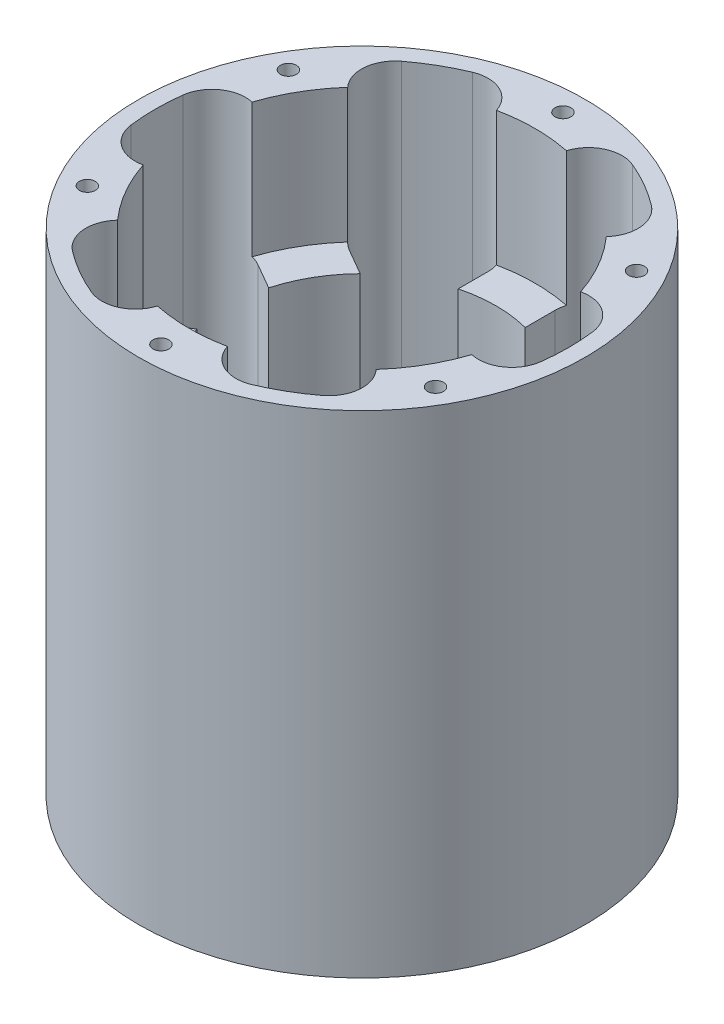
SolidWorks part; units mm, degrees
material "6061-T6 (SS)"
ref_plane "Front Plane" through (0, 0, 0) normal (0, 0, 1) x (1, 0, 0)
ref_plane "Top Plane" through (0, 0, 0) normal (0, 1, 0) x (1, 0, 0)
ref_plane "Right Plane" through (0, 0, 0) normal (1, 0, 0) x (0, 0, -1)
sketch "Sketch1" plane through (0, 0, 0) normal (0, 1, 0) x (1, 0, 0)
  circle A0 centre (0, 0) radius 31.75
  circle A1 centre (0, 0) radius 19.05
  dimension "D1" = 63.5
  dimension "D2" = 38.1
extrude "Boss-Extrude1" add sketch "Sketch1" along normal mid plane 69.85
sketch "Sketch2" plane through (0, 34.925, 0) normal (0, 1, 0) x (1, 0, 0)
  circle A0 centre (0, 0) radius 24.6062
  dimension "D1" = 49.2125
extrude "Cut-Extrude1" cut sketch "Sketch2" against normal blind 19.05
sketch "Sketch3" plane through (0, -34.925, 0) normal (0, -1, 0) x (1, 0, 0)
  circle A0 centre (0, 0) radius 24.6062
  dimension "D1" = 49.2125
extrude "Cut-Extrude2" cut sketch "Sketch3" against normal blind 30.48
hole_wizard "#4-40 Tapped Hole1" positions "Sketch5" profile "Sketch6" tap size "#4-40" standard "Ansi Inch" end condition through all
sketch "Sketch5" plane through (0, 34.925, 0) normal (0, 1, 0) x (-1, 0, 0)
  point P0 (0, 28.575)
  point P13 (24.7467, 14.2875)
  point P14 (24.7467, -14.2875)
  point P15 (0, -28.575)
  point P16 (-24.7467, -14.2875)
  point P17 (-24.7467, 14.2875)
  dimension "D1" = 28.575
  dimension "D2" = 6
sketch "Sketch6" plane through (0, 34.925, 28.575) normal (1, 0, 0) x (0, 0, 1)
  line L0 (0, 0) -> (0, 69.85)
  line L1 (0, 69.85) -> (1.1303, 69.85)
  line L2 (1.1303, 69.85) -> (1.1303, 0)
  line L5 (1.1303, 0) -> (0, 0)
  line L11 (0, -6.35) -> (0, 107.95) construction
  dimension "Thread Major Dia." = 2.2606
  dimension "Thru Tap Drill Depth" = 69.85
sketch "Sketch7" plane through (0, -34.925, 0) normal (0, -1, 0) x (1, 0, 0)
  line L0 (0, 19.05) -> (0, 29.3687) construction
  line L1 (4.7625, 18.4451) -> (4.7625, 28.98)
  line L2 (-4.7625, 18.4451) -> (-4.7625, 28.98)
  line L3 (-4.7625, 19.05) -> (-4.7625, 29.3687) construction
  line L4 (4.7625, 19.05) -> (4.7625, 29.3687) construction
  line L5 (18.3552, 5.0981) -> (27.4787, 10.3656)
  line L6 (16.4978, 9.525) -> (25.4341, 14.6844) construction
  line L7 (13.5927, 13.347) -> (22.7162, 18.6145)
  line L8 (13.5927, -13.347) -> (22.7162, -18.6145)
  line L9 (16.4978, -9.525) -> (25.4341, -14.6844) construction
  line L10 (18.3552, -5.0981) -> (27.4787, -10.3656)
  line L11 (-4.7625, -18.4451) -> (-4.7625, -28.98)
  line L12 (0, -19.05) -> (0, -29.3687) construction
  line L13 (4.7625, -18.4451) -> (4.7625, -28.98)
  line L14 (-18.3552, -5.0981) -> (-27.4787, -10.3656)
  line L15 (-16.4978, -9.525) -> (-25.4341, -14.6844) construction
  line L16 (-13.5927, -13.347) -> (-22.7162, -18.6145)
  line L17 (-13.5927, 13.347) -> (-22.7162, 18.6145)
  line L18 (-16.4978, 9.525) -> (-25.4341, 14.6844) construction
  line L19 (-18.3552, 5.0981) -> (-27.4787, 10.3656)
  arc A0 (-4.7625, 28.98) -> (-22.7162, 18.6145) centre (0, 0) ccw
  circle A1 centre (0, 0) radius 31.75 construction
  arc A2 (13.5927, 13.347) -> (4.7625, 18.4451) centre (0, 0) ccw
  circle A3 centre (0, 0) radius 19.05 construction
  arc A4 (22.7162, 18.6145) -> (4.7625, 28.98) centre (0, 0) ccw
  arc A5 (-4.7625, 18.4451) -> (-13.5927, 13.347) centre (0, 0) ccw
  arc A6 (27.4787, -10.3656) -> (27.4787, 10.3656) centre (0, 0) ccw
  arc A7 (18.3552, -5.0981) -> (18.3552, 5.0981) centre (0, 0) ccw
  arc A8 (4.7625, -28.98) -> (22.7162, -18.6145) centre (0, 0) ccw
  arc A9 (4.7625, -18.4451) -> (13.5927, -13.347) centre (0, 0) ccw
  arc A10 (-22.7162, -18.6145) -> (-4.7625, -28.98) centre (0, 0) ccw
  arc A11 (-13.5927, -13.347) -> (-4.7625, -18.4451) centre (0, 0) ccw
  arc A12 (-18.3552, 5.0981) -> (-18.3552, -5.0981) centre (0, 0) ccw
  arc A13 (-27.4787, 10.3656) -> (-27.4787, -10.3656) centre (0, 0) ccw
  dimension "D1" = 2.3813
  dimension "D2" = 4.7625
  dimension "D3" = 4.7625
  dimension "D4" = 6
extrude "Cut-Extrude3" cut sketch "Sketch7" against normal through all
fillet "Fillet1" radius 4.7625 12 edges at (-22.7162, 0, -18.6145) (-4.7625, 0, -28.98) (4.7625, 0, -28.98) (22.7162, 0, -18.6145) (27.4787, 0, -10.3656) (27.4787, 0, 10.3656) (22.7162, 0, 18.6145) (4.7625, 0, 28.98) (-4.7625, 0, 28.98) (-22.7162, 0, 18.6145) (-27.4787, 0, -10.3656) (-27.4787, 0, 10.3656)
